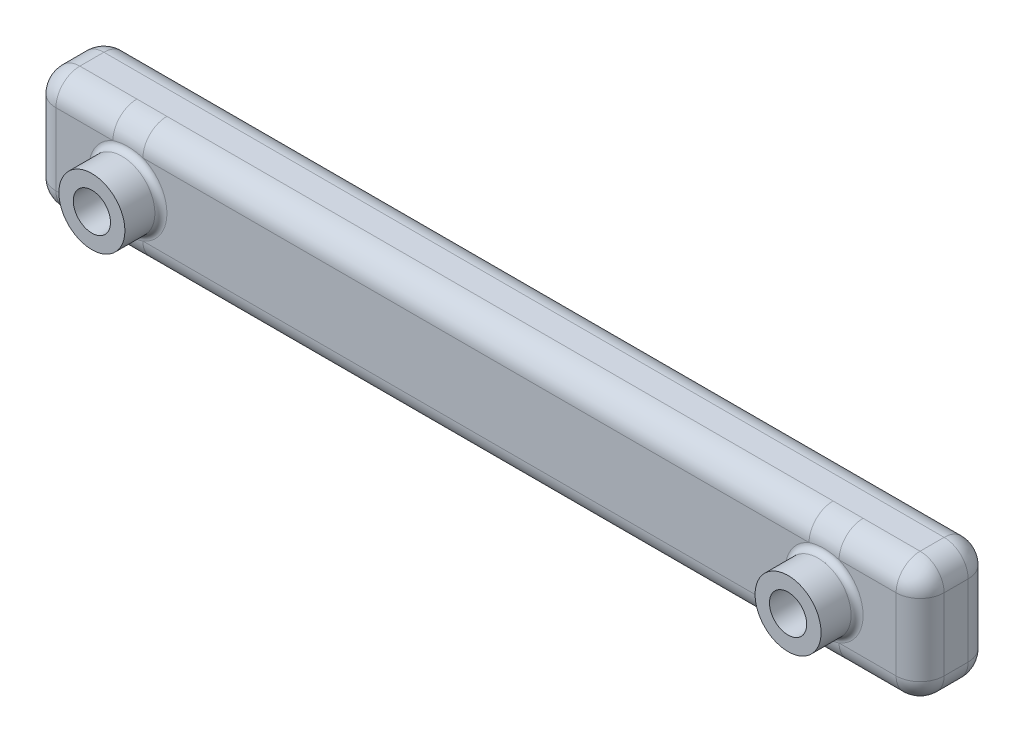
SolidWorks part; units mm, degrees
ref_plane "前视基准面" through (0, 0, 0) normal (0, 0, 1) x (1, 0, 0)
ref_plane "上视基准面" through (0, 0, 0) normal (0, 1, 0) x (1, 0, 0)
ref_plane "右视基准面" through (0, 0, 0) normal (1, 0, 0) x (0, 0, -1)
sketch "草图1" plane through (0, 0, 0) normal (0, 0, 1) x (1, 0, 0)
  line L1 (-24.0996, 6.3351) -> (49.9004, 6.3351)
  line L2 (-24.0996, 6.3351) -> (-24.0996, -3.6649)
  line L3 (-24.0996, -3.6649) -> (49.9004, -3.6649)
  line L4 (49.9004, 6.3351) -> (49.9004, -3.6649)
  dimension "D1" = 74
  dimension "D2" = 10
extrude "凸台-拉伸1" add sketch "草图1" along normal blind 6
sketch "草图2" plane through (0, 0, 6) normal (0, 0, 1) x (1, 0, 0)
  line L0 (-24.0996, 1.3351) -> (55.6004, 1.3351) construction
  line L1 (-24.0996, 6.3351) -> (-24.0996, -3.6649) construction
  line L2 (12.9004, -8.7036) -> (12.9004, 14.3252) construction
  circle A0 centre (-16.0996, 1.3351) radius 1.55
  circle A1 centre (41.9004, 1.3351) radius 1.55
  dimension "D4" = 3.1
  dimension "D5" = 3.1
  dimension "D1" = 29
  dimension "D2" = 29
  dimension "D3" = 37
extrude "切除-拉伸1" cut sketch "草图2" against normal blind 10
sketch "草图3" plane through (0, 0, 6) normal (0, 0, 1) x (1, 0, 0)
  circle A0 centre (-16.0996, 1.3351) radius 2.75
  circle A1 centre (41.9004, 1.3351) radius 2.75
  circle A2 centre (-16.0996, 1.3351) radius 1.55
  circle A3 centre (41.9004, 1.3351) radius 1.55
  dimension "D1" = 5.5
  dimension "D2" = 5.5
extrude "凸台-拉伸2" add sketch "草图3" along normal blind 3
fillet "圆角5" radius 0.5 1 edges at (44.6504, 1.3351, 6)
fillet "圆角7" radius 0.5 1 edges at (-13.3496, 1.3351, 6)
sketch "草图4" plane through (0, 0, 0) normal (0, 0, -1) x (-1, 0, 0)
  line L1 (-38.3785, 1.3351) -> (-40.1395, 4.3851)
  line L2 (-40.1395, 4.3851) -> (-43.6613, 4.3851)
  line L3 (-43.6613, 4.3851) -> (-45.4222, 1.3351)
  line L4 (-45.4222, 1.3351) -> (-43.6613, -1.7149)
  line L5 (-43.6613, -1.7149) -> (-40.1395, -1.7149)
  line L6 (-40.1395, -1.7149) -> (-38.3785, 1.3351)
  line L7 (19.1977, 3.01) -> (16.1982, 4.8556)
  line L8 (16.1982, 4.8556) -> (13.1001, 3.1807)
  line L9 (13.1001, 3.1807) -> (13.0015, -0.3397)
  line L10 (13.0015, -0.3397) -> (16.001, -2.1853)
  line L11 (16.001, -2.1853) -> (19.0991, -0.5105)
  line L12 (19.0991, -0.5105) -> (19.1977, 3.01)
  circle A0 centre (-41.9004, 1.3351) radius 3.05 construction
  circle A1 centre (16.0996, 1.3351) radius 3.05 construction
  dimension "D1" = 6.1
  dimension "D2" = 6.1
extrude "切除-拉伸2" cut sketch "草图4" against normal blind 2.5
fillet "圆角8" radius 2 12 edges at (-24.0996, 1.3351, 0) (12.9004, -3.6649, 0) (49.9004, 1.3351, 0) (12.9004, 6.3351, 0) (12.9004, -3.6649, 6) (49.9004, 1.3351, 6) (12.9004, 6.3351, 6) (-24.0996, 6.3351, 3) (49.9004, 6.3351, 3) (49.9004, -3.6649, 3) (-24.0996, -3.6649, 3) (-24.0996, 1.3351, 6)
